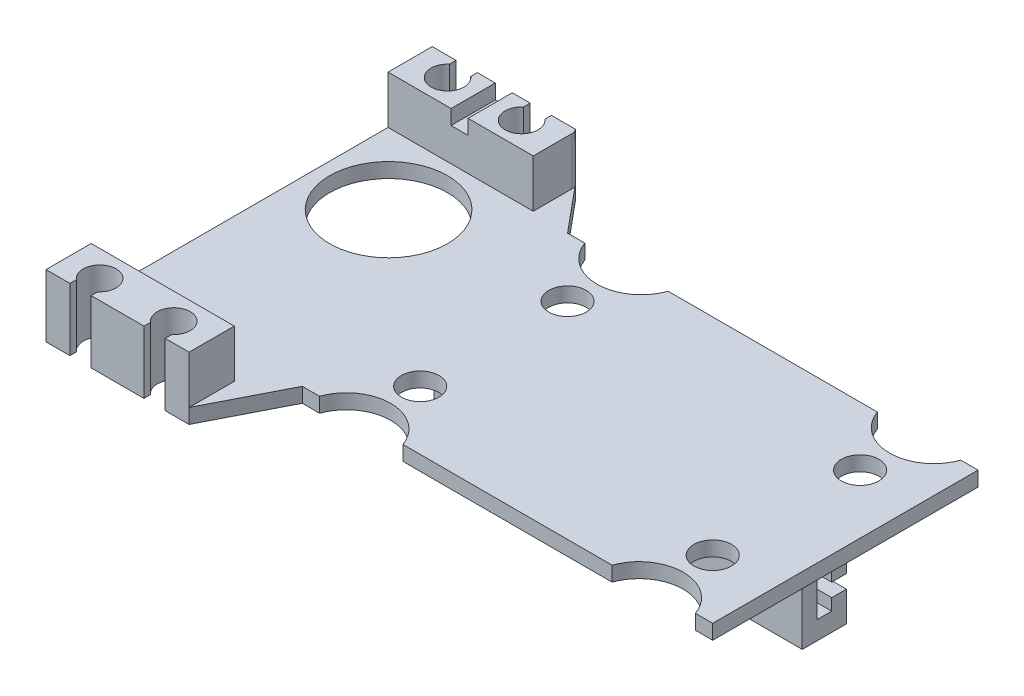
SolidWorks part; units mm, degrees
ref_plane "Front Plane" through (0, 0, 0) normal (0, 0, 1) x (1, 0, 0)
ref_plane "Top Plane" through (0, 0, 0) normal (0, 1, 0) x (1, 0, 0)
ref_plane "Right Plane" through (0, 0, 0) normal (1, 0, 0) x (0, 0, -1)
sketch "Sketch1" plane through (0, 0, 0) normal (1, 0, 0) x (0, 0, -1)
  line L0 (0, 0) -> (6.25, 0)
  line L2 (4, 2.5) -> (2, 2.5)
  line L3 (2, 2.5) -> (2, 7.5)
  line L4 (2, 7.5) -> (4, 7.5)
  line L6 (6.25, 10) -> (0, 10)
  line L7 (0, 10) -> (0, 0)
  line L8 (4, 7.5) -> (4, 5.9125)
  line L9 (4, 5.9125) -> (6, 5.9125)
  line L10 (6, 5.9125) -> (6, 10)
  line L11 (6, 10) -> (6.25, 10)
  line L12 (4, 2.5) -> (4, 4.0875)
  line L13 (4, 4.0875) -> (6, 4.0875)
  line L14 (6, 4.0875) -> (6, 0)
  line L15 (6, 0) -> (6.25, 0)
  dimension "D1" = 5
  dimension "D2" = 1.5875
  dimension "D3" = 2
  dimension "D4" = 2
  dimension "D5" = 2
  dimension "D6" = 10
extrude "Boss-Extrude1" add sketch "Sketch1" along normal blind 50 contours L14 L13 L12 L2 L3 L4 L8 L9 L10 L6 L7 L0 region at (0, 5, -0.1166)
sketch "Sketch2" plane through (0, 10, 0) normal (0, 1, 0) x (1, 0, 0)
  line L1 (-2.85, -15) -> (52.85, -15)
  line L2 (-2.85, -15) -> (-2.85, 21)
  line L3 (-2.85, 21) -> (52.85, 21)
  line L4 (52.85, -15) -> (52.85, 21)
  line L5 (0, 3) -> (50, 3) construction
  line L6 (0, 6) -> (0, 0) construction
  line L7 (50, 6) -> (50, 0) construction
  line L8 (-2.85, 3) -> (52.85, 3) construction
  line L9 (25, 21) -> (25, -15) construction
  line L10 (25, 6) -> (25, 0) construction
  line L11 (50, 6) -> (0, 6) construction
  line L12 (50, 0) -> (0, 0) construction
  line L13 (5.15, -7) -> (44.85, -7) construction
  line L14 (5.15, 13) -> (44.85, 13) construction
  circle A0 centre (5.15, 13) radius 2.55
  circle A1 centre (44.85, 13) radius 2.55
  circle A2 centre (44.85, -7) radius 2.55
  circle A3 centre (5.15, -7) radius 2.55
  dimension "D1" = 5.1
  dimension "D2" = 39.7
  dimension "D3" = 20
  dimension "D4" = 39.7
  dimension "D5" = 8
  dimension "D6" = 8
  dimension "D7" = 8
extrude "Boss-Extrude2" add sketch "Sketch2" along normal blind 2
sketch "Sketch6" plane through (0, 10, 0) normal (0, -1, 0) x (1, 0, 0)
  line L1 (-8.0429, -27.2452) -> (-27.4571, -27.2452)
  line L3 (-8.0429, 25.169) -> (-27.4571, 25.169)
  line L4 (-27.4571, -27.2452) -> (-27.4571, 25.169)
  line L6 (-2.85, -21) -> (-2.85, 15)
  line L9 (-8.0429, -27.2452) -> (-2.85, -21)
  line L10 (-2.85, 15) -> (-8.0429, 25.169)
  arc A0 (-8.75, -27.5381) -> (-7.75, -26.5381) centre (-8.75, -26.5381) ccw construction
  arc A1 (-26.75, 25.4619) -> (-27.75, 24.4619) centre (-26.75, 24.4619) ccw construction
  circle A2 centre (-17.75, -11.6131) radius 8
  point P14 (0, 0)
  dimension "D1" = 16
extrude "Boss-Extrude5" add sketch "Sketch6" against normal blind 2
sketch "Sketch7" plane through (0, 12, 0) normal (0, 1, 0) x (1, 0, 0)
  line L0 (-7.75, 26.5381) -> (-7.75, 20.1131) construction
  line L1 (-27.4571, 27.2452) -> (-7.75, 27.2452)
  line L2 (-27.4571, 27.2452) -> (-27.4571, 21.2452)
  line L3 (-27.4571, 21.2452) -> (-7.75, 21.2452)
  line L4 (-7.75, 27.2452) -> (-7.75, 21.2452)
  line L15 (-27.75, 26.5381) -> (-27.75, 20.1131)
  line L16 (-26.75, 21.1131) -> (-8.75, 21.1131)
  line L17 (-7.75, 20.1131) -> (-7.75, 26.5381)
  line L18 (-8.75, 27.5381) -> (-11.285, 27.5381)
  line L19 (-11.285, 27.5381) -> (-11.285, 26.3473)
  line L20 (-14.165, 26.3473) -> (-14.165, 27.5381)
  line L21 (-14.165, 27.5381) -> (-21.335, 27.5381)
  line L22 (-21.335, 27.5381) -> (-21.335, 26.3473)
  line L23 (-24.215, 26.3473) -> (-24.215, 27.5381)
  line L24 (-24.215, 27.5381) -> (-26.75, 27.5381)
  line L25 (-27.75, 26.5381) -> (-27.75, 20.1131)
  line L26 (-26.75, 21.1131) -> (-8.75, 21.1131)
  line L27 (-7.75, 20.1131) -> (-7.75, 26.5381)
  line L28 (-8.75, 27.5381) -> (-11.285, 27.5381)
  line L29 (-11.285, 27.5381) -> (-11.285, 26.3473)
  line L30 (-14.165, 26.3473) -> (-14.165, 27.5381)
  line L31 (-14.165, 27.5381) -> (-21.335, 27.5381)
  line L32 (-21.335, 27.5381) -> (-21.335, 26.3473)
  line L33 (-24.215, 26.3473) -> (-24.215, 27.5381)
  line L34 (-24.215, 27.5381) -> (-26.75, 27.5381)
  arc A0 (-24.215, 26.3473) -> (-21.335, 26.3473) centre (-22.775, 24.6381) ccw construction
  arc A1 (-24.215, 26.3473) -> (-21.335, 26.3473) centre (-22.775, 24.6381) ccw
  arc A2 (-14.165, 26.3473) -> (-11.285, 26.3473) centre (-12.725, 24.6381) ccw construction
  arc A3 (-14.165, 26.3473) -> (-11.285, 26.3473) centre (-12.725, 24.6381) ccw
  arc A10 (-26.75, 21.1131) -> (-27.75, 20.1131) centre (-26.75, 20.1131) ccw
  arc A11 (-7.75, 20.1131) -> (-8.75, 21.1131) centre (-8.75, 20.1131) ccw
  arc A12 (-7.75, 26.5381) -> (-8.75, 27.5381) centre (-8.75, 26.5381) ccw
  arc A13 (-14.165, 26.3473) -> (-11.285, 26.3473) centre (-12.725, 24.6381) ccw
  arc A14 (-24.215, 26.3473) -> (-21.335, 26.3473) centre (-22.775, 24.6381) ccw
  arc A15 (-26.75, 27.5381) -> (-27.75, 26.5381) centre (-26.75, 26.5381) ccw
  arc A16 (-26.75, 21.1131) -> (-27.75, 20.1131) centre (-26.75, 20.1131) ccw
  arc A17 (-7.75, 20.1131) -> (-8.75, 21.1131) centre (-8.75, 20.1131) ccw
  arc A18 (-7.75, 26.5381) -> (-8.75, 27.5381) centre (-8.75, 26.5381) ccw
  arc A19 (-14.165, 26.3473) -> (-11.285, 26.3473) centre (-12.725, 24.6381) ccw
  arc A20 (-24.215, 26.3473) -> (-21.335, 26.3473) centre (-22.775, 24.6381) ccw
  arc A21 (-26.75, 27.5381) -> (-27.75, 26.5381) centre (-26.75, 26.5381) ccw
  line M22 (-2.85, 21) -> (-8.0429, 27.2452)
  line M23 (-8.0429, 27.2452) -> (-27.4571, 27.2452)
  line M24 (-27.4571, 27.2452) -> (-27.4571, -25.169)
  dimension "D1" = 6
  dimension "D2" = 0
extrude "Boss-Extrude6" add sketch "Sketch7" along normal blind 6.5 contours L4 A18 L29 A3 L30 L32 A1 L33 L3 M22 M23 M24 region at (-17.5508, 12, -23.9953)
sketch "Sketch8" plane through (0, 18.5, 0) normal (0, 1, 0) x (1, 0, 0)
  line L0 (-18.4, 27.5381) -> (-18.4, 21.1131) construction
  line L1 (-17.1, 27.5381) -> (-17.1, 21.1131) construction
  line L2 (-18.4, 27.5381) -> (-18.4, 21.1131) construction
  line L3 (-17.1, 27.5381) -> (-17.1, 21.1131) construction
  line L4 (-18.4, 27.5381) -> (-17.1, 27.5381) construction
  line L5 (-18.4, 21.1131) -> (-17.1, 21.1131) construction
  line L6 (-18.9, 28.0381) -> (-16.6, 28.0381)
  line L7 (-16.6, 28.0381) -> (-16.6, 20.6131)
  line L8 (-18.9, 20.6131) -> (-16.6, 20.6131)
  line L9 (-18.9, 28.0381) -> (-18.9, 20.6131)
  dimension "D1" = 0.5
extrude "Cut-Extrude1" cut sketch "Sketch8" against normal blind 2
sketch "Sketch9" plane through (0, 12, 0) normal (0, 1, 0) x (1, 0, 0)
  line L0 (-18.9, 21.2452) -> (-18.9, 27.2452) construction
  line L1 (-18.9, 27.2452) -> (-21.335, 27.2452) construction
  line L2 (-21.335, 27.2452) -> (-21.335, 26.3473) construction
  line L3 (-24.215, 26.3473) -> (-24.215, 27.2452) construction
  line L4 (-24.215, 27.2452) -> (-27.4571, 27.2452) construction
  line L5 (-27.4571, 27.2452) -> (-27.4571, 21.2452) construction
  line L6 (-27.4571, 21.2452) -> (-18.9, 21.2452) construction
  line L7 (-16.6, 27.2452) -> (-16.6, 21.2452) construction
  line L8 (-16.6, 21.2452) -> (-7.75, 21.2452) construction
  line L9 (-7.75, 21.2452) -> (-7.75, 26.5381) construction
  line L10 (-7.9257, 27.1043) -> (-8.0429, 27.2452) construction
  line L11 (-8.0429, 27.2452) -> (-11.285, 27.2452) construction
  line L12 (-11.285, 27.2452) -> (-11.285, 26.3473) construction
  line L13 (-14.165, 26.3473) -> (-14.165, 27.2452) construction
  line L14 (-14.165, 27.2452) -> (-16.6, 27.2452) construction
  line L15 (-18.9, 21.2452) -> (-18.9, 27.2452)
  line L16 (-18.9, 27.2452) -> (-21.335, 27.2452)
  line L17 (-21.335, 27.2452) -> (-21.335, 26.3473)
  line L18 (-24.215, 26.3473) -> (-24.215, 27.2452)
  line L19 (-24.215, 27.2452) -> (-27.4571, 27.2452)
  line L20 (-27.4571, 27.2452) -> (-27.4571, 21.2452)
  line L21 (-27.4571, 21.2452) -> (-18.9, 21.2452)
  line L22 (-16.6, 27.2452) -> (-16.6, 21.2452)
  line L23 (-16.6, 21.2452) -> (-7.75, 21.2452)
  line L24 (-7.75, 21.2452) -> (-7.75, 26.5381)
  line L25 (-7.9257, 27.1043) -> (-8.0429, 27.2452)
  line L26 (-8.0429, 27.2452) -> (-11.285, 27.2452)
  line L27 (-11.285, 27.2452) -> (-11.285, 26.3473)
  line L28 (-14.165, 26.3473) -> (-14.165, 27.2452)
  line L29 (-14.165, 27.2452) -> (-16.6, 27.2452)
  line L30 (-11.285, 27.2452) -> (-14.165, 27.2452)
  line L31 (-24.215, 27.2452) -> (-21.335, 27.2452)
  line L32 (-14.165, 27.2452) -> (-11.285, 27.2452)
  arc A0 (-24.215, 26.3473) -> (-21.335, 26.3473) centre (-22.775, 24.6381) ccw construction
  arc A1 (-7.75, 26.5381) -> (-7.9257, 27.1043) centre (-8.75, 26.5381) ccw construction
  arc A2 (-14.165, 26.3473) -> (-11.285, 26.3473) centre (-12.725, 24.6381) ccw construction
  arc A3 (-24.215, 26.3473) -> (-21.335, 26.3473) centre (-22.775, 24.6381) ccw
  arc A4 (-7.75, 26.5381) -> (-7.9257, 27.1043) centre (-8.75, 26.5381) ccw
  arc A5 (-14.165, 26.3473) -> (-11.285, 26.3473) centre (-12.725, 24.6381) ccw
  line M1 (-14.165, 27.2452) -> (-14.165, 26.3473)
  arc M2 (-14.165, 26.3473) -> (-11.285, 26.3473) centre (-12.725, 24.6381) ccw
  line M3 (-11.285, 26.3473) -> (-11.285, 27.2452)
  line M4 (-11.285, 27.2452) -> (-14.165, 27.2452)
extrude "Cut-Extrude2" cut sketch "Sketch9" against normal up to surface (2 mm away) contours M4 M1 M2 M3 | L18 A3 L17 L31 region at (-22.775, 12, -24.8463) region at (-12.725, 12, -24.8463) up to face at (25, 10, -3)
sketch "Sketch11" plane through (0, 10, 0) normal (0, -1, 0) x (1, 0, 0)
  line L0 (-14.165, 25.4619) -> (-17.1, 25.4619) construction
  line L2 (-17.1, 19.0369) -> (-8.75, 19.0369) construction
  line L3 (-7.75, 18.0369) -> (-7.75, 24.4619) construction
  line L4 (-8.75, 25.4619) -> (-11.285, 25.4619) construction
  line L5 (-11.285, 25.4619) -> (-11.285, 24.2712) construction
  line L6 (-14.165, 24.2712) -> (-14.165, 25.4619) construction
  line L8 (-18.4, 25.4619) -> (-21.335, 25.4619) construction
  line L9 (-21.335, 25.4619) -> (-21.335, 24.2712) construction
  line L10 (-24.215, 24.2712) -> (-24.215, 25.4619) construction
  line L11 (-24.215, 25.4619) -> (-26.75, 25.4619) construction
  line L12 (-27.75, 24.4619) -> (-27.75, 18.0369) construction
  line L13 (-26.75, 19.0369) -> (-18.4, 19.0369) construction
  line L14 (-14.165, 25.4619) -> (-17.1, 25.4619)
  line L16 (-17.1, 19.0369) -> (-8.75, 19.0369)
  line L17 (-7.75, 18.0369) -> (-7.75, 24.4619)
  line L18 (-8.75, 25.4619) -> (-11.285, 25.4619)
  line L19 (-11.285, 25.4619) -> (-11.285, 24.2712)
  line L20 (-14.165, 24.2712) -> (-14.165, 25.4619)
  line L22 (-18.4, 25.4619) -> (-21.335, 25.4619)
  line L23 (-21.335, 25.4619) -> (-21.335, 24.2712)
  line L24 (-24.215, 24.2712) -> (-24.215, 25.4619)
  line L25 (-24.215, 25.4619) -> (-26.75, 25.4619)
  line L26 (-27.75, 24.4619) -> (-27.75, 18.0369)
  line L27 (-26.75, 19.0369) -> (-18.4, 19.0369)
  line L28 (-17.1, 19.0369) -> (-18.4, 19.0369)
  line L29 (-17.1, 25.4619) -> (-18.4, 25.4619)
  line L30 (-27.4571, 25.169) -> (-27.4571, -27.2452) construction
  line L31 (-8.0429, 25.169) -> (-27.4571, 25.169)
  line L32 (-8.0429, 25.169) -> (-8.0429, 19.0369)
  line L33 (-8.0429, 19.0369) -> (-27.4571, 19.0369)
  line L34 (-27.4571, 25.169) -> (-27.4571, 19.0369)
  arc A0 (-7.75, 18.0369) -> (-8.75, 19.0369) centre (-8.75, 18.0369) ccw construction
  arc A1 (-7.75, 24.4619) -> (-8.75, 25.4619) centre (-8.75, 24.4619) ccw construction
  arc A2 (-14.165, 24.2712) -> (-11.285, 24.2712) centre (-12.725, 22.5619) ccw construction
  arc A3 (-24.215, 24.2712) -> (-21.335, 24.2712) centre (-22.775, 22.5619) ccw construction
  arc A4 (-26.75, 25.4619) -> (-27.75, 24.4619) centre (-26.75, 24.4619) ccw construction
  arc A5 (-26.75, 19.0369) -> (-27.75, 18.0369) centre (-26.75, 18.0369) ccw construction
  arc A6 (-7.75, 18.0369) -> (-8.75, 19.0369) centre (-8.75, 18.0369) ccw
  arc A7 (-7.75, 24.4619) -> (-8.75, 25.4619) centre (-8.75, 24.4619) ccw
  arc A8 (-14.165, 24.2712) -> (-11.285, 24.2712) centre (-12.725, 22.5619) ccw
  arc A9 (-24.215, 24.2712) -> (-21.335, 24.2712) centre (-22.775, 22.5619) ccw
  arc A10 (-26.75, 25.4619) -> (-27.75, 24.4619) centre (-26.75, 24.4619) ccw
  arc A11 (-26.75, 19.0369) -> (-27.75, 18.0369) centre (-26.75, 18.0369) ccw
  line M36 (-8.0429, 25.169) -> (-27.4571, 25.169)
  line M37 (-27.4571, 25.169) -> (-27.4571, -27.2452)
extrude "Boss-Extrude7" add sketch "Sketch11" against normal blind 8.5 contours A9 L24 L33 L27 L28 L16 L32 L19 A8 L20 L23 M36 M37 region at (-17.75, 10, 21.8309)
sketch "Sketch12" plane through (0, 10, 0) normal (0, -1, 0) x (1, 0, 0)
  line L0 (-11.285, 25.169) -> (-14.165, 25.169)
  line L1 (-21.335, 25.169) -> (-24.215, 25.169)
  line L10 (-21.335, 25.169) -> (-21.335, 24.2712)
  line L11 (-14.165, 25.169) -> (-21.335, 25.169)
  line L12 (-14.165, 24.2712) -> (-14.165, 25.169)
  line L13 (-11.285, 25.169) -> (-11.285, 24.2712)
  line L14 (-8.0429, 25.169) -> (-11.285, 25.169)
  line L15 (-8.0429, 19.0369) -> (-8.0429, 25.169)
  line L16 (-27.4571, 19.0369) -> (-8.0429, 19.0369)
  line L17 (-27.4571, 25.169) -> (-27.4571, 19.0369)
  line L18 (-24.215, 25.169) -> (-27.4571, 25.169)
  line L19 (-24.215, 24.2712) -> (-24.215, 25.169)
  line L20 (-21.335, 25.169) -> (-21.335, 24.2712)
  line L21 (-14.165, 25.169) -> (-21.335, 25.169)
  line L22 (-14.165, 24.2712) -> (-14.165, 25.169)
  line L23 (-11.285, 25.169) -> (-11.285, 24.2712)
  line L24 (-8.0429, 25.169) -> (-11.285, 25.169)
  line L25 (-8.0429, 19.0369) -> (-8.0429, 25.169)
  line L26 (-27.4571, 19.0369) -> (-8.0429, 19.0369)
  line L27 (-27.4571, 25.169) -> (-27.4571, 19.0369)
  line L28 (-24.215, 25.169) -> (-27.4571, 25.169)
  line L29 (-24.215, 24.2712) -> (-24.215, 25.169)
  arc A2 (-24.215, 24.2712) -> (-21.335, 24.2712) centre (-22.775, 22.5619) ccw
  arc A3 (-14.165, 24.2712) -> (-11.285, 24.2712) centre (-12.725, 22.5619) ccw
  arc A4 (-24.215, 24.2712) -> (-21.335, 24.2712) centre (-22.775, 22.5619) ccw
  arc A5 (-14.165, 24.2712) -> (-11.285, 24.2712) centre (-12.725, 22.5619) ccw
  line M14 (-8.0429, 25.169) -> (-27.4571, 25.169)
  dimension "D1" = 0
extrude "Cut-Extrude3" cut sketch "Sketch12" against normal up to surface (2 mm away) contours L29 A4 L20 M14 | L22 A5 L23 M14 region at (-12.725, 10, 22.7701) region at (-22.775, 10, 22.7701) up to face at (5.15, 12, -10.45)
sketch "Sketch13" plane through (0, 10, 0) normal (0, -1, 0) x (1, 0, 0)
  line L0 (44.85, -13) -> (44.85, 7) construction
  line L1 (5.15, -13) -> (5.15, 7) construction
  circle A0 centre (44.85, -23) radius 6
  circle A1 centre (44.85, 17) radius 6
  circle A2 centre (5.15, 17) radius 6
  circle A3 centre (5.15, -23) radius 6
  dimension "D2" = 12
  dimension "D1" = 10
  dimension "D3" = 10
  dimension "D4" = 10
  dimension "D5" = 10
extrude "Cut-Extrude4" cut sketch "Sketch13" against normal up to surface (2 mm away) contours A2 | A1 | A0 | A3 up to face at (5.15, 12, -10.45)
